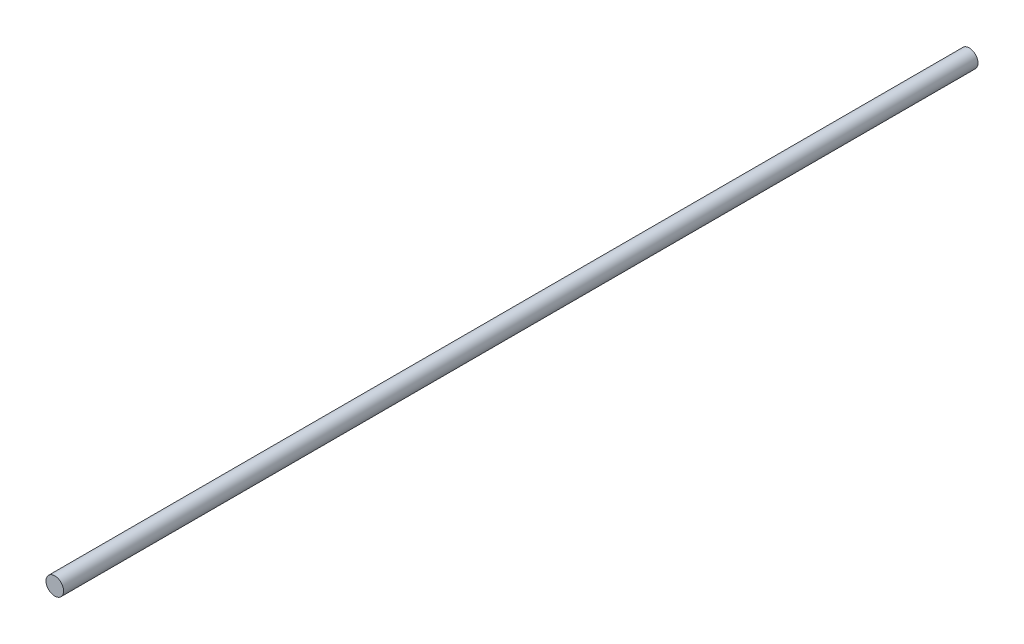
SolidWorks part; units mm, degrees
material "AISI 1015 Steel, Cold Drawn (SS)"
ref_plane "Front Plane" through (0, 0, 0) normal (0, 0, 1) x (1, 0, 0)
ref_plane "Top Plane" through (0, 0, 0) normal (0, 1, 0) x (1, 0, 0)
ref_plane "Right Plane" through (0, 0, 0) normal (1, 0, 0) x (0, 0, -1)
sketch "Sketch1" plane through (0, 0, 0) normal (0, 0, 1) x (1, 0, 0)
  line L0 (-304.8, 3.175) -> (304.8, 3.175) construction
  circle A0 centre (-177.8, 28.575) radius 6.35
  dimension "D1" = 12.7
  dimension "D2" = 25.4
  dimension "D3" = 177.8
extrude "Boss-Extrude1" add sketch "Sketch1" along normal offset from surface (660.4397 mm away) 127
